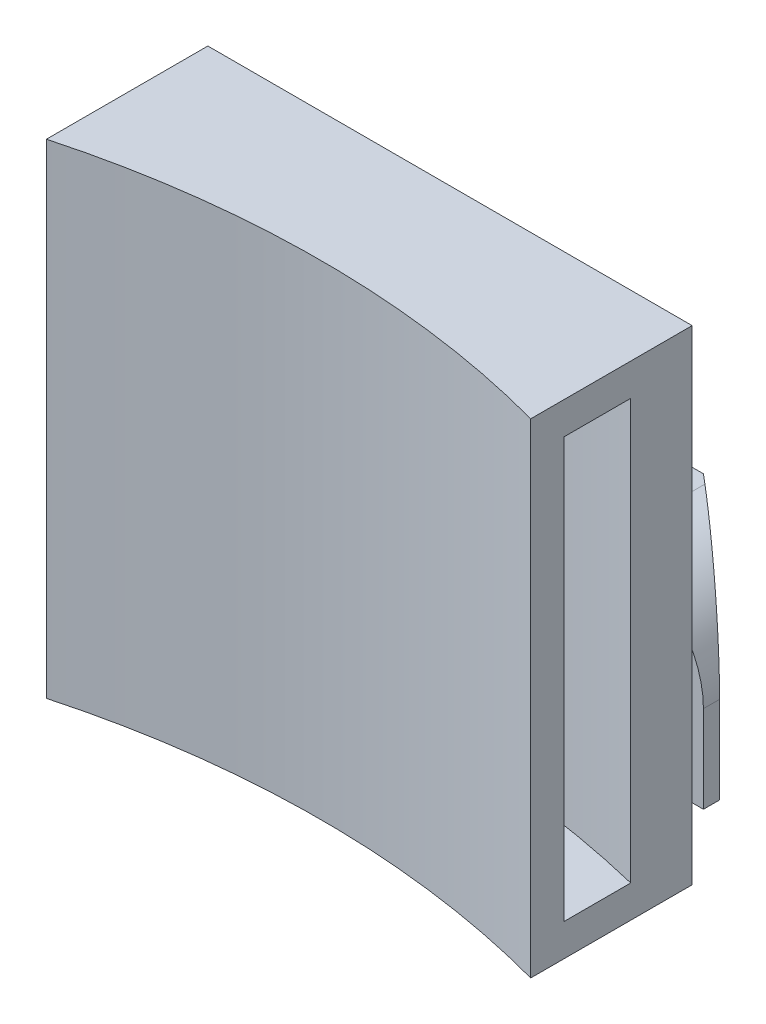
SolidWorks part; units mm, degrees
ref_plane "Front Plane" through (0, 0, 0) normal (0, 0, 1) x (1, 0, 0)
ref_plane "Top Plane" through (0, 0, 0) normal (0, 1, 0) x (1, 0, 0)
ref_plane "Right Plane" through (0, 0, 0) normal (1, 0, 0) x (0, 0, -1)
sketch "Sketch1" plane through (0, 0, 0) normal (0, 1, 0) x (1, 0, 0)
  line L0 (-2.35, 5.5) -> (2.35, 5.5)
  line L1 (2.35, 5.5) -> (5.65, 2.7)
  line L2 (5.65, 2.7) -> (5.65, 2.2)
  line L3 (5.65, 2.2) -> (2.5, 2.2)
  line L4 (2.5, 2.2) -> (2.5, 0)
  line L5 (2.5, 0) -> (7.5, 0)
  line L6 (7.5, 0) -> (7.5, -5)
  line L7 (0, -55) -> (0, 55) construction
  line L8 (-7.5, 0) -> (-7.5, -5)
  line L9 (-2.5, 0) -> (-7.5, 0)
  line L10 (-2.5, 2.2) -> (-2.5, 0)
  line L11 (-5.65, 2.2) -> (-2.5, 2.2)
  line L12 (-5.65, 2.7) -> (-5.65, 2.2)
  line L13 (-2.35, 5.5) -> (-5.65, 2.7)
  arc A0 (7.5, -5) -> (-7.5, -5) centre (0, -32.625) ccw
  dimension "D1" = 2.2
  dimension "D2" = 4.7
  dimension "D3" = 5.5
  dimension "D4" = 11.3
  dimension "D5" = 0.5
  dimension "D6" = 5
  dimension "D7" = 15
  dimension "D8" = 4
  dimension "D9" = 5
extrude "Boss-Extrude1" add sketch "Sketch1" along normal mid plane 15
sketch "Sketch2" plane through (0, 7.5, 0) normal (0, 1, 0) x (1, 0, 0)
  line L0 (-2.5, 0) -> (2.5, 0)
  line L13 (-2.35, 5.5) -> (-5.65, 2.7)
  line L14 (-5.65, 2.7) -> (-5.65, 2.2)
  line L15 (-5.65, 2.2) -> (-2.5, 2.2)
  line L16 (-2.5, 2.2) -> (-2.5, 0)
  line L17 (-2.5, 0) -> (-7.5, 0)
  line L18 (-7.5, 0) -> (-7.5, -5)
  line L19 (7.5, -5) -> (7.5, 0)
  line L20 (7.5, 0) -> (2.5, 0)
  line L21 (2.5, 0) -> (2.5, 2.2)
  line L22 (2.5, 2.2) -> (5.65, 2.2)
  line L23 (5.65, 2.2) -> (5.65, 2.7)
  line L24 (5.65, 2.7) -> (2.35, 5.5)
  line L25 (2.35, 5.5) -> (-2.35, 5.5)
  line L26 (-2.35, 5.5) -> (-5.65, 2.7)
  line L27 (-5.65, 2.7) -> (-5.65, 2.2)
  line L28 (-5.65, 2.2) -> (-2.5, 2.2)
  line L29 (-2.5, 2.2) -> (-2.5, 0)
  line L34 (2.5, 0) -> (2.5, 2.2)
  line L35 (2.5, 2.2) -> (5.65, 2.2)
  line L36 (5.65, 2.2) -> (5.65, 2.7)
  line L37 (5.65, 2.7) -> (2.35, 5.5)
  line L38 (2.35, 5.5) -> (-2.35, 5.5)
  arc A1 (7.5, -5) -> (-7.5, -5) centre (0, -32.625) ccw
  dimension "D1" = 0
extrude "Cut-Extrude2" cut sketch "Sketch2" against normal offset from surface (9.3 mm away) 5.7 up to face at (0, -7.5, -1.1571)
fillet "Fillet1" radius 3 4 edges at (-5.65, -7.5, -2.45) (-2.5, -7.5, -1.1) (5.65, -1.8, -2.45) (2.5, -1.8, -1.1)
fillet "Fillet2" radius 0.7 9 edges at (-1.6213, -6.6213, -2.2) (2.5, -6.15, -2.2) (-1.6213, -6.6213, 0) (2.5, -6.15, 0) (1.6213, -2.6787, 0) (-2.5, -3.15, -2.2) (1.6213, -2.6787, -2.2) (-2.5, -3.15, 0) (-1.5, -1.8, 0)
sketch "Sketch3" plane through (0, 0, 0) normal (0, 0, -1) x (-1, 0, 0)
  line L0 (-7.5, 7.5) -> (7.5, 7.5) construction
  line L1 (3, 3.5) -> (-3, 3.5)
  line L2 (3, 3.5) -> (3, 7.5)
  line L3 (3, 7.5) -> (-3, 7.5)
  line L4 (-3, 3.5) -> (-3, 7.5)
  line L5 (3, 3.5) -> (-3, 7.5) construction
  line L6 (3, 7.5) -> (-3, 3.5) construction
  point P0 (0, 5.5)
  dimension "D1" = 4
  dimension "D2" = 6
extrude "Boss-Extrude2" add sketch "Sketch3" along normal blind 1 draft 45
sketch "Sketch5" plane through (0, 0, 0) normal (0, 0, -1) x (-1, 0, 0)
  line L0 (0, 5.775) -> (0, -5.775) construction
  line L1 (3, 7.5) -> (7.5, 7.5) construction
  circle A0 centre (6, 5.5) radius 0.75
  circle A1 centre (-6, 5.5) radius 0.75
  point P6 (6, -8.046)
  point P7 (6, 5.3135)
  dimension "D1" = 1.5
  dimension "D2" = 12
  dimension "D3" = 2
extrude "Boss-Extrude3" add sketch "Sketch5" along normal blind 0.6 draft 35
sketch "Sketch6" plane through (0, 0, 0) normal (0, 1, 0) x (1, 0, 0)
  line L4 (-7.5, 0) -> (-7.5, -5) construction
  line L5 (-7.5, -1.9022) -> (-7.5, -3.9651)
  line L6 (7.5, -5) -> (7.5, 0) construction
  line L7 (7.5, -3.9651) -> (7.5, -1.9022)
  arc A0 (7.762, -4.0349) -> (-7.762, -4.0349) centre (0, -32.625) ccw construction
  arc A1 (7.5, -5) -> (-7.5, -5) centre (0, -32.625) ccw construction
  arc A2 (7.5, -5) -> (-7.5, -5) centre (0, -32.625) ccw construction
  arc A3 (7.5, -3.9651) -> (-7.5, -3.9651) centre (0, -32.625) ccw
  arc A4 (7.5, -1.9022) -> (-7.5, -1.9022) centre (0, -32.625) ccw
  arc A5 (8.286, -2.1048) -> (-8.286, -2.1048) centre (0, -32.625) ccw construction
  dimension "D1" = 1
  dimension "D2" = 2
extrude "Cut-Extrude3" cut sketch "Sketch6" against normal mid plane 13
